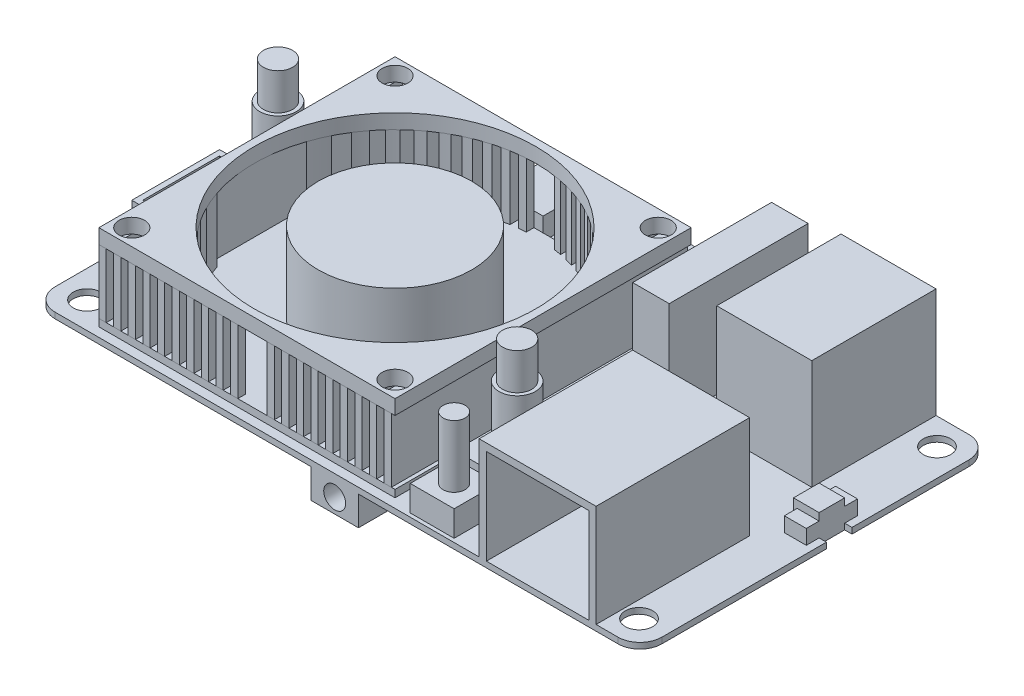
SolidWorks part; units mm, degrees
ref_plane "Front Plane" through (0, 0, 0) normal (0, 0, 1) x (1, 0, 0)
ref_plane "Top Plane" through (0, 0, 0) normal (0, 1, 0) x (1, 0, 0)
ref_plane "Right Plane" through (0, 0, 0) normal (1, 0, 0) x (0, 0, -1)
sketch "Sketch1" plane through (0, 0, 0) normal (0, 1, 0) x (1, 0, 0)
  line L0 (0, 0) -> (-83, 0)
  line L1 (-83, 0) -> (-83, 48)
  line L2 (-83, 48) -> (0, 48)
  line L3 (0, 48) -> (0, 0)
  line L4 (0, 24) -> (-83, 24) construction
  circle A0 centre (-79.25, 44.375) radius 1.875
  circle A1 centre (-79.25, 3.625) radius 1.875
  circle A2 centre (-3.75, 44.375) radius 1.875
  circle A3 centre (-3.75, 3.625) radius 1.875
  dimension "D1" = 20.375
  dimension "D2" = 20.375
  dimension "D3" = 3.75
  dimension "D4" = 3.75
  dimension "D5" = 83
  dimension "D6" = 48
extrude "Boss-Extrude1" add sketch "Sketch1" along normal blind 0.8
fillet "Fillet1" radius 3 4 edges at (-83, 0.4, -48) (0, 0.4, -48) (0, 0.4, 0) (-83, 0.4, 0)
sketch "Sketch2" plane through (0, 0.8, 0) normal (0, 1, 0) x (1, 0, 0)
  line L0 (-82.5, 13) -> (-77.4321, 13)
  line L1 (-77.4321, 13) -> (-77.4321, 25)
  line L2 (-77.4321, 25) -> (-82.5, 25)
  line L3 (-82.5, 25) -> (-82.5, 13)
  line L4 (-74, 40.5) -> (-74, 0)
  line L5 (-74, 0) -> (-33.5, 0)
  line L6 (-33.5, 0) -> (-33.5, 40.5)
  line L7 (-33.5, 40.5) -> (-74, 40.5)
  line L8 (-74, 20.25) -> (-53.75, 20.25) construction
  line L9 (-53.75, 20.25) -> (-53.75, 40.5) construction
  line L10 (-83, 45) -> (-83, 3) construction
  line L11 (-80, 0) -> (-3, 0) construction
  line L12 (-22, 0) -> (-22, 21)
  line L13 (-22, 21) -> (-6, 21)
  line L14 (-6, 21) -> (-6, 0)
  line L15 (-6, 0) -> (-22, 0)
  line L16 (-30, 48) -> (-30, 29)
  line L17 (-3, 48) -> (-80, 48) construction
  line L18 (-30, 29) -> (-25, 29)
  line L19 (-25, 29) -> (-25, 48)
  line L20 (-25, 48) -> (-30, 48)
  line L21 (-20.5, 48) -> (-20.5, 31)
  line L22 (-20.5, 31) -> (-7.5, 31)
  line L23 (-7.5, 31) -> (-7.5, 48)
  line L24 (-7.5, 48) -> (-20.5, 48)
  line L25 (0, 3) -> (0, 45) construction
  line L26 (-78.5, 32.5) -> (-74, 32.5)
  line L27 (-78.5, 25.5) -> (-74, 25.5)
  line L28 (-29, 15.7056) -> (-33.5, 15.7056)
  line L29 (-31.9171, 0.5) -> (-31.9171, 6.5)
  line L30 (-29, 8.7056) -> (-33.5, 8.7056)
  line L31 (-31.9171, 6.5) -> (-25.9171, 6.5)
  line L32 (-25.9171, 6.5) -> (-25.9171, 0.5)
  line L33 (-25.9171, 0.5) -> (-31.9171, 0.5)
  line L34 (-31.9171, 3.5) -> (-28.2034, 3.5) construction
  line L35 (-28.9171, 6.5) -> (-28.9171, 3.5) construction
  line L36 (-75.5, 43.75) -> (-68.5, 43.75)
  line L37 (-68.5, 43.75) -> (-68.5, 48.75)
  line L38 (-68.5, 48.75) -> (-75.5, 48.75)
  line L39 (-75.5, 48.75) -> (-75.5, 43.75)
  line L40 (-61.5, 41.75) -> (-61.5, 48.75)
  line L41 (-61.5, 48.75) -> (-55, 48.75)
  line L42 (-55, 48.75) -> (-55, 41.75)
  line L43 (-55, 41.75) -> (-61.5, 41.75)
  line L44 (-42, 48) -> (-42, 40.5)
  line L45 (-42, 40.5) -> (-37, 40.5)
  line L46 (-37, 40.5) -> (-37, 48)
  line L47 (-37, 48) -> (-42, 48)
  line L48 (0, 29) -> (-1, 29)
  line L49 (-1, 29) -> (-1, 25.5)
  line L50 (-1, 25.5) -> (0, 25.5)
  line L51 (-1, 29) -> (-1, 30.75)
  line L52 (-1, 30.75) -> (-4, 30.75)
  line L53 (-4, 30.75) -> (-4, 29)
  line L54 (-4, 29) -> (-4.5, 29)
  line L55 (-4.5, 29) -> (-4.5, 25.5)
  line L56 (-4.5, 25.5) -> (-4, 25.5)
  line L57 (-4, 25.5) -> (-4, 23.75)
  line L58 (-4, 23.75) -> (-1, 23.75)
  line L59 (-1, 23.75) -> (-1, 25.5)
  line L60 (-29, 27.25) -> (-29, 20.25)
  line L61 (-29, 20.25) -> (-27, 20.25)
  line L62 (-29, 27.25) -> (-27, 27.25)
  line L63 (-27, 27.25) -> (-27, 25.5)
  line L64 (-27, 25.5) -> (-26.5, 25.5)
  line L65 (-26.5, 25.5) -> (-26.5, 22)
  line L66 (-26.5, 22) -> (-27, 22)
  line L67 (-27, 22) -> (-27, 20.25)
  line L68 (-4, 29) -> (-1, 29)
  line L69 (-4, 25.5) -> (-1, 25.5)
  line L70 (-27, 25.5) -> (-29, 25.5)
  line L71 (-27, 22) -> (-29, 22)
  circle A0 centre (-53.75, 20.25) radius 19.25
  circle A1 centre (-71.75, 38.25) radius 1.75
  circle A2 centre (-35.75, 38.25) radius 1.75
  circle A3 centre (-35.75, 2.25) radius 1.75
  circle A4 centre (-71.75, 2.25) radius 1.75
  circle A5 centre (-53.75, 20.25) radius 10.5
  circle A6 centre (-78.5, 29) radius 2
  circle A7 centre (-28.9171, 3.5) radius 1.5
  circle A8 centre (-29, 12.2056) radius 2.5
  circle A9 centre (-78.5, 29) radius 2.5
  circle A10 centre (-78.5, 29) radius 3.5
  circle A11 centre (-29, 12.2056) radius 2
  circle A12 centre (-29, 12.2056) radius 3.5
  line M5 (-3, 48) -> (-80, 48)
  line M9 (-80, 0) -> (-3, 0)
  line M11 (0, 3) -> (0, 45)
  dimension "D1" = 9
  dimension "D3" = 2.25
  dimension "D5" = 6
  dimension "D17" = 4.5
  dimension "D18" = 0.5
  dimension "D19" = 6.5
  dimension "D35" = 1.75
  dimension "D2" = 0
  dimension "D4" = 2.25
  dimension "D6" = 16
  dimension "D7" = 21
  dimension "D8" = 13
  dimension "D9" = 5
  dimension "D10" = 4.5
  dimension "D11" = 7.5
  dimension "D12" = 0.5
  dimension "D13" = 13
  dimension "D14" = 12
  dimension "D15" = 4
  dimension "D16" = 4.5
  dimension "D20" = 7
  dimension "D21" = 0.75
  dimension "D22" = 0.75
  dimension "D23" = 1
  dimension "D24" = 3.5
  dimension "D25" = 19
  dimension "D26" = 17
  dimension "D27" = 19
  dimension "D28" = 7
  dimension "D29" = 5
  dimension "D30" = 13
  dimension "D31" = 7
  dimension "D32" = 7.5
  dimension "D33" = 7
  dimension "D34" = 5
  dimension "D36" = 2
  dimension "D37" = 3.5
  dimension "D38" = 1.75
  dimension "D39" = 0.5
extrude "Boss-Extrude2" add sketch "Sketch2" along normal blind 2 from offset 11 separate body contours L6 L7 L4 A0 M9 region at (-58, 0.8, -39.9272)
extrude "Boss-Extrude3" add sketch "Sketch2<3>" along normal blind 15 contours L22 L23 L21 M5 region at (-14, 0.8, -39.5)
sketch "Sketch2<3>" plane through (0, 0.8, 0) normal (0, 1, 0) x (1, 0, 0) same geometry as "Sketch2"
extrude "Boss-Extrude4" add sketch "Sketch2<4>" along normal blind 14 contours L14 L13 L12 M9 region at (-14, 0.8, -10.5)
sketch "Sketch2<4>" plane through (0, 0.8, 0) normal (0, 1, 0) x (1, 0, 0) same geometry as "Sketch2"
extrude "Boss-Extrude5" add sketch "Sketch2<5>" along normal blind 14 contours L18 L19 L16 M5 region at (-27.5, 0.8, -38.5)
sketch "Sketch2<5>" plane through (0, 0.8, 0) normal (0, 1, 0) x (1, 0, 0) same geometry as "Sketch2"
extrude "Boss-Extrude6" add sketch "Sketch2<6>" along normal blind 12 contours A7
sketch "Sketch2<6>" plane through (0, 0.8, 0) normal (0, 1, 0) x (1, 0, 0) same geometry as "Sketch2"
extrude "Boss-Extrude7" add sketch "Sketch2<7>" along normal blind 3.5 contours L33 L32 L31 L29 A7 region at (-31.8322, 0.8, -3.5)
sketch "Sketch2<7>" plane through (0, 0.8, 0) normal (0, 1, 0) x (1, 0, 0) same geometry as "Sketch2"
extrude "Boss-Extrude8" add sketch "Sketch2<8>" along normal blind 2.5 contours L39 L36 L37 M5 | L38 L39 L37 M5 region at (-72, 0.8, -45.875) region at (-72, 0.8, -48.375)
sketch "Sketch2<8>" plane through (0, 0.8, 0) normal (0, 1, 0) x (1, 0, 0) same geometry as "Sketch2"
extrude "Boss-Extrude9" add sketch "Sketch2<9>" along normal blind 3 contours L43 L42 L40 M5 | L42 L41 L40 M5 region at (-58.25, 0.8, -44.875) region at (-58.25, 0.8, -48.375)
sketch "Sketch2<9>" plane through (0, 0.8, 0) normal (0, 1, 0) x (1, 0, 0) same geometry as "Sketch2"
extrude "Boss-Extrude10" add sketch "Sketch2<10>" along normal blind 3.5 contours L7 L46 L44 M5 region at (-39.5, 0.8, -44.25)
sketch "Sketch2<10>" plane through (0, 0.8, 0) normal (0, 1, 0) x (1, 0, 0) same geometry as "Sketch2"
extrude "Boss-Extrude11" add sketch "Sketch2<11>" along normal blind 1 from offset 1.25 contours A10 L27 L4 L26 | A12 L28 L6 L30 | A10 | L7 L4 L5 L6 | A12 region at (-74.0832, 0.8, -29) region at (-31.25, 0.8, -15.6224)
sketch "Sketch2<11>" plane through (0, 0.8, 0) normal (0, 1, 0) x (1, 0, 0) same geometry as "Sketch2"
extrude "Boss-Extrude12" add sketch "Sketch2<12>" along normal blind 9 from surface contours A9 A6 | A8 A11 region at (-31.4293, 0.8, -12.2056) region at (-80.9293, 0.8, -29) starting at face at (-51.7143, 3.05, -23.3445)
sketch "Sketch2<12>" plane through (0, 0.8, 0) normal (0, 1, 0) x (1, 0, 0) same geometry as "Sketch2"
extrude "Boss-Extrude14" add sketch "Sketch2<13>" along normal blind 14 from offset 2.25 contours A6 | A11 region at (-78.5, 0.8, -29) region at (-29, 0.8, -12.2056)
sketch "Sketch2<13>" plane through (0, 0.8, 0) normal (0, 1, 0) x (1, 0, 0) same geometry as "Sketch2"
extrude "Boss-Extrude15" add sketch "Sketch2<14>" along normal blind 3 contours L58 L59 L49 L51 L52 L53 L54 L55 L56 L57 region at (-2.75, 0.8, -27.25)
sketch "Sketch2<14>" plane through (0, 0.8, 0) normal (0, 1, 0) x (1, 0, 0) same geometry as "Sketch2"
extrude "Cut-Extrude1" cut sketch "Sketch2<15>" against normal blind 3 contours L49 L50 L48 M11 region at (-0.5, 0.8, -27.25)
sketch "Sketch2<15>" plane through (0, 0.8, 0) normal (0, 1, 0) x (1, 0, 0) same geometry as "Sketch2"
extrude "Boss-Extrude16" add sketch "Sketch2<16>" along normal blind 2 contours L53 L68 L51 L52 | L69 L57 L58 L59 region at (-2.5, 0.8, -29.875) region at (-2.5, 0.8, -24.625)
sketch "Sketch2<16>" plane through (0, 0.8, 0) normal (0, 1, 0) x (1, 0, 0) same geometry as "Sketch2"
extrude "Boss-Extrude17" add sketch "Sketch2<17>" along normal blind 2 contours L67 L66 L65 L64 L63 L62 L60 L61 | L67 L71 L60 L61 | L70 L63 L62 L60 region at (-28, 0.8, -26.375) region at (-27.75, 0.8, -23.75) region at (-28, 0.8, -21.125)
sketch "Sketch2<17>" plane through (0, 0.8, 0) normal (0, 1, 0) x (1, 0, 0) same geometry as "Sketch2"
extrude "Boss-Extrude18" add sketch "Sketch2<18>" along normal blind 6 contours L71 L66 L65 L64 L70 L60 region at (-27.75, 0.8, -23.75)
sketch "Sketch2<18>" plane through (0, 0.8, 0) normal (0, 1, 0) x (1, 0, 0) same geometry as "Sketch2"
extrude "Boss-Extrude19" add sketch "Sketch2<19>" along normal blind 5.5 contours L2 L3 L0 L1 region at (-79.9661, 0.8, -19)
sketch "Sketch2<19>" plane through (0, 0.8, 0) normal (0, 1, 0) x (1, 0, 0) same geometry as "Sketch2"
chamfer "Chamfer1" distance 1 angle 45 1 edges at (-77.4321, 3.55, -25)
sketch "Sketch3" plane through (0, 3.05, 0) normal (0, 1, 0) x (1, 0, 0)
  line L0 (-74, 32.5) -> (-74, 25.5)
  line L1 (-73, 40.5) -> (-73, 32.5)
  line L2 (-73, 32.5) -> (-73, 25.5)
  line L3 (-73, 25.5) -> (-73, 0)
  line L4 (-72, 40.5) -> (-72, 32.5)
  line L5 (-72, 32.5) -> (-72, 25.5)
  line L6 (-72, 25.5) -> (-72, 0)
  line L7 (-71, 40.5) -> (-71, 32.5)
  line L8 (-71, 32.5) -> (-71, 25.5)
  line L9 (-71, 25.5) -> (-71, 0)
  line L10 (-70, 40.5) -> (-70, 32.5)
  line L11 (-70, 32.5) -> (-70, 25.5)
  line L12 (-74, 32.5) -> (-78.5, 32.5)
  line L13 (-78.5, 25.5) -> (-74, 25.5)
  line L14 (-74, 25.5) -> (-74, 0)
  line L15 (-74, 0) -> (-33.5, 0)
  line L16 (-33.5, 0) -> (-33.5, 8.7056)
  line L17 (-33.5, 8.7056) -> (-29, 8.7056)
  line L18 (-29, 15.7056) -> (-33.5, 15.7056)
  line L19 (-33.5, 15.7056) -> (-33.5, 40.5)
  line L20 (-33.5, 40.5) -> (-37, 40.5)
  line L21 (-37, 40.5) -> (-42, 40.5)
  line L22 (-42, 40.5) -> (-74, 40.5)
  line L23 (-74, 40.5) -> (-74, 32.5)
  line L24 (-74, 32.5) -> (-78.5, 32.5)
  line L25 (-78.5, 25.5) -> (-74, 25.5)
  line L26 (-74, 25.5) -> (-74, 0)
  line L27 (-74, 0) -> (-33.5, 0)
  line L28 (-33.5, 0) -> (-33.5, 8.7056)
  line L29 (-33.5, 8.7056) -> (-29, 8.7056)
  line L30 (-29, 15.7056) -> (-33.5, 15.7056)
  line L31 (-33.5, 15.7056) -> (-33.5, 40.5)
  line L32 (-33.5, 40.5) -> (-37, 40.5)
  line L33 (-37, 40.5) -> (-42, 40.5)
  line L34 (-42, 40.5) -> (-74, 40.5)
  line L35 (-74, 40.5) -> (-74, 32.5)
  line L36 (-70, 25.5) -> (-70, 0)
  line L37 (-69, 40.5) -> (-69, 32.5)
  line L38 (-69, 32.5) -> (-69, 25.5)
  line L39 (-69, 25.5) -> (-69, 0)
  line L40 (-68, 40.5) -> (-68, 32.5)
  line L41 (-68, 32.5) -> (-68, 25.5)
  line L42 (-68, 25.5) -> (-68, 0)
  line L43 (-67, 40.5) -> (-67, 32.5)
  line L44 (-67, 32.5) -> (-67, 25.5)
  line L45 (-67, 25.5) -> (-67, 0)
  line L46 (-66, 40.5) -> (-66, 32.5)
  line L47 (-66, 32.5) -> (-66, 25.5)
  line L48 (-66, 25.5) -> (-66, 0)
  line L49 (-65, 40.5) -> (-65, 32.5)
  line L50 (-65, 32.5) -> (-65, 25.5)
  line L51 (-65, 25.5) -> (-65, 0)
  line L52 (-64, 40.5) -> (-64, 32.5)
  line L53 (-64, 32.5) -> (-64, 25.5)
  line L54 (-64, 25.5) -> (-64, 0)
  line L55 (-63, 40.5) -> (-63, 32.5)
  line L56 (-63, 32.5) -> (-63, 25.5)
  line L57 (-63, 25.5) -> (-63, 0)
  line L58 (-62, 40.5) -> (-62, 32.5)
  line L59 (-62, 32.5) -> (-62, 25.5)
  line L60 (-62, 25.5) -> (-62, 0)
  line L61 (-61, 40.5) -> (-61, 32.5)
  line L62 (-61, 32.5) -> (-61, 25.5)
  line L63 (-61, 25.5) -> (-61, 0)
  line L64 (-60, 40.5) -> (-60, 32.5)
  line L65 (-60, 32.5) -> (-60, 25.5)
  line L66 (-60, 25.5) -> (-60, 0)
  line L67 (-59, 40.5) -> (-59, 32.5)
  line L68 (-59, 32.5) -> (-59, 25.5)
  line L69 (-59, 25.5) -> (-59, 0)
  line L70 (-58, 40.5) -> (-58, 32.5)
  line L71 (-58, 32.5) -> (-58, 25.5)
  line L72 (-58, 25.5) -> (-58, 0)
  line L73 (-57, 40.5) -> (-57, 32.5)
  line L74 (-57, 32.5) -> (-57, 25.5)
  line L75 (-57, 25.5) -> (-57, 0)
  line L76 (-56, 40.5) -> (-56, 32.5)
  line L77 (-56, 32.5) -> (-56, 25.5)
  line L78 (-56, 25.5) -> (-56, 0)
  line L79 (-55, 40.5) -> (-55, 32.5)
  line L80 (-55, 32.5) -> (-55, 25.5)
  line L81 (-55, 25.5) -> (-55, 0)
  line L82 (-54, 40.5) -> (-54, 32.5)
  line L83 (-54, 32.5) -> (-54, 25.5)
  line L84 (-54, 25.5) -> (-54, 0)
  line L85 (-53, 40.5) -> (-53, 32.5)
  line L86 (-53, 32.5) -> (-53, 25.5)
  line L87 (-53, 25.5) -> (-53, 0)
  line L88 (-52, 40.5) -> (-52, 32.5)
  line L89 (-52, 32.5) -> (-52, 25.5)
  line L90 (-52, 25.5) -> (-52, 0)
  line L91 (-51, 40.5) -> (-51, 32.5)
  line L92 (-51, 32.5) -> (-51, 25.5)
  line L93 (-51, 25.5) -> (-51, 0)
  line L94 (-50, 40.5) -> (-50, 32.5)
  line L95 (-50, 32.5) -> (-50, 25.5)
  line L96 (-50, 25.5) -> (-50, 0)
  line L97 (-49, 40.5) -> (-49, 32.5)
  line L98 (-49, 32.5) -> (-49, 25.5)
  line L99 (-49, 25.5) -> (-49, 0)
  line L100 (-48, 40.5) -> (-48, 32.5)
  line L101 (-48, 32.5) -> (-48, 25.5)
  line L102 (-48, 25.5) -> (-48, 0)
  line L103 (-47, 40.5) -> (-47, 32.5)
  line L104 (-47, 32.5) -> (-47, 25.5)
  line L105 (-47, 25.5) -> (-47, 0)
  line L106 (-46, 40.5) -> (-46, 32.5)
  line L107 (-46, 32.5) -> (-46, 25.5)
  line L108 (-46, 25.5) -> (-46, 0)
  line L109 (-45, 40.5) -> (-45, 32.5)
  line L110 (-45, 32.5) -> (-45, 25.5)
  line L111 (-45, 25.5) -> (-45, 0)
  line L112 (-44, 40.5) -> (-44, 32.5)
  line L113 (-44, 32.5) -> (-44, 25.5)
  line L114 (-44, 25.5) -> (-44, 0)
  line L115 (-43, 40.5) -> (-43, 32.5)
  line L116 (-43, 32.5) -> (-43, 25.5)
  line L117 (-43, 25.5) -> (-43, 0)
  line L118 (-42, 40.5) -> (-42, 32.5)
  line L119 (-42, 32.5) -> (-42, 25.5)
  line L120 (-42, 25.5) -> (-42, 0)
  line L121 (-41, 40.5) -> (-41, 32.5)
  line L122 (-41, 32.5) -> (-41, 25.5)
  line L123 (-41, 25.5) -> (-41, 0)
  line L124 (-40, 40.5) -> (-40, 32.5)
  line L125 (-40, 32.5) -> (-40, 25.5)
  line L126 (-40, 25.5) -> (-40, 0)
  line L127 (-39, 40.5) -> (-39, 32.5)
  line L128 (-39, 32.5) -> (-39, 25.5)
  line L129 (-39, 25.5) -> (-39, 0)
  line L130 (-38, 40.5) -> (-38, 32.5)
  line L131 (-38, 32.5) -> (-38, 25.5)
  line L132 (-38, 25.5) -> (-38, 0)
  line L133 (-37, 40.5) -> (-37, 32.5)
  line L134 (-37, 32.5) -> (-37, 25.5)
  line L135 (-37, 25.5) -> (-37, 0)
  line L136 (-36, 40.5) -> (-36, 32.5)
  line L137 (-36, 32.5) -> (-36, 25.5)
  line L138 (-36, 25.5) -> (-36, 0)
  line L139 (-35, 40.5) -> (-35, 32.5)
  line L140 (-35, 32.5) -> (-35, 25.5)
  line L141 (-35, 25.5) -> (-35, 0)
  line L142 (-34, 40.5) -> (-34, 32.5)
  line L143 (-34, 32.5) -> (-34, 25.5)
  line L144 (-34, 25.5) -> (-34, 0)
  circle A0 centre (-53.75, 20.25) radius 19.25 construction
  circle A1 centre (-53.75, 20.25) radius 19.25
  arc A2 (-78.5, 32.5) -> (-78.5, 25.5) centre (-78.5, 29) ccw
  arc A3 (-29, 8.7056) -> (-29, 15.7056) centre (-29, 12.2056) ccw
  arc A4 (-78.5, 32.5) -> (-78.5, 25.5) centre (-78.5, 29) ccw
  arc A5 (-29, 8.7056) -> (-29, 15.7056) centre (-29, 12.2056) ccw
  line M139 (-74, 25.5) -> (-74, 0)
  line M140 (-74, 0) -> (-33.5, 0)
  line M148 (-42, 40.5) -> (-74, 40.5)
  line M149 (-74, 40.5) -> (-74, 32.5)
  dimension "D2" = 41
  dimension "D1" = 0
extrude "Boss-Extrude23" add sketch "Sketch3" along normal blind 8.75 separate body contours L3 L2 L1 L0 M148 M149 M139 M140 | A1 L6 L9 M140 | A1 L36 L27 L39 | A1 L42 L27 L45 | A1 L48 L27 L51 | A1 L54 L27 L57 | A1 L60 L27 L63 | A1 L66 L27 L69 | A1 L72 L27 L75 | A1 L78 L27 L81 | A1 L8 L7 L4 L5 M148 | A1 L38 L37 L34 L10 L11 | A1 L43 L34 L40 | A1 L49 L34 L46 | A1 L55 L34 L52 | A1 L61 L34 L58 | A1 L67 L34 L64 | A1 L73 L34 L70 | A1 L79 L34 L76 | A1 L93 L96 M140 | A1 L99 L102 M140 | A1 L105 L108 M140 | A1 L111 L114 M140 | A1 L117 L120 M140 | A1 L123 L126 M140 | A1 L129 L132 M140 | A1 L135 L138 M140 | A1 L141 L144 L143 L142 L32 L139 L140 M140 | A1 L137 L136 L32 L133 L134 | A1 L131 L130 L33 L127 | A1 L124 L33 L121 | A1 L118 L115 M148 | A1 L112 L34 L109 | A1 L106 L34 L103 | A1 L100 L34 L97 | A1 L94 L34 L91 region at (-73.5, 3.05, -20.25) region at (-71.5156, 3.05, -34.062) region at (-71.5156, 3.05, -6.438) region at (-69.5129, 3.05, -35.8941) region at (-69.5129, 3.05, -4.6059) region at (-67.5125, 3.05, -37.1015) region at (-67.5125, 3.05, -3.3985) region at (-65.5128, 3.05, -37.9918) region at (-65.5128, 3.05, -2.5082) region at (-63.5134, 3.05, -38.6685) region at (-63.5134, 3.05, -1.8315) region at (-61.5139, 3.05, -39.181) region at (-61.5139, 3.05, -1.319) region at (-59.5139, 3.05, -39.5572) region at (-59.5139, 3.05, -0.9428) region at (-57.5121, 3.05, -39.8133) region at (-57.5121, 3.05, -0.6867) region at (-55.507, 3.05, -39.9587) region at (-55.507, 3.05, -0.5413) region at (-50.4888, 3.05, -39.8597) region at (-50.4888, 3.05, -0.6403) region at (-48.4864, 3.05, -39.632) region at (-48.4864, 3.05, -0.868) region at (-46.486, 3.05, -39.2871) region at (-46.486, 3.05, -1.2129) region at (-44.4865, 3.05, -38.8107) region at (-44.4865, 3.05, -1.6893) region at (-42.487, 3.05, -38.1786) region at (-42.487, 3.05, -2.3214) region at (-40.4874, 3.05, -37.3483) region at (-40.4874, 3.05, -3.1517) region at (-38.4873, 3.05, -36.2356) region at (-38.4873, 3.05, -4.2644) region at (-36.4856, 3.05, -34.6198) region at (-36.4856, 3.05, -5.8802) region at (-34.4768, 3.05, -20.25)
extrude "Boss-Extrude24" add sketch "Sketch2<20>" along normal blind 11 from surface contours A5 region at (-53.75, 0.8, -20.25) starting at face at (-51.7143, 3.05, -23.3445)
sketch "Sketch2<20>" plane through (0, 0.8, 0) normal (0, 1, 0) x (1, 0, 0) same geometry as "Sketch2"
sketch "Sketch4" plane through (0, 0, 0) normal (0, -1, 0) x (1, 0, 0)
  line L0 (-82.5, -41) -> (-78, -41)
  line L1 (-78, -41) -> (-78, -32.5)
  line L2 (-78, -32.5) -> (-82.5, -32.5)
  line L3 (-82.5, -32.5) -> (-82.5, -41)
  line L4 (-74.5, -10) -> (-74.5, -15)
  line L5 (-74.5, -15) -> (-63.5, -15)
  line L6 (-63.5, -15) -> (-63.5, -10)
  line L7 (-63.5, -10) -> (-74.5, -10)
  line L8 (-63, -2) -> (-63, -20)
  line L9 (-63, -20) -> (-50, -20)
  line L10 (-50, -20) -> (-50, -2)
  line L11 (-50, -2) -> (-63, -2)
  line L12 (-62, -3.5) -> (-62, -16.5)
  line L13 (-62, -16.5) -> (-51, -16.5)
  line L14 (-51, -16.5) -> (-51, -3.5)
  line L15 (-51, -3.5) -> (-62, -3.5)
  line L16 (-45, -13) -> (-45, 0)
  line L17 (-45, 0) -> (-38.5, 0)
  line L18 (-80, 0) -> (-3, 0) construction
  line L19 (-38.5, 0) -> (-38.5, -13)
  line L20 (-45, -13) -> (-38.5, -13)
  line L21 (-83, -45) -> (-83, -3) construction
  line L22 (-3, -48) -> (-80, -48) construction
  line L23 (-6, -21) -> (-6, 0) construction
  line L24 (-6, -21) -> (-6, 0)
  line L25 (-22, 0) -> (-22, -21) construction
  line L26 (-22, 0) -> (-22, -21)
  circle A0 centre (-20.25, -10) radius 1.5
  circle A1 centre (-7.75, -10) radius 1.5
  circle A2 centre (-29, -12.2056) radius 2 construction
  circle A3 centre (-78.5, -29) radius 2 construction
  circle A4 centre (-29, -12.2056) radius 2
  circle A5 centre (-78.5, -29) radius 2
  circle A6 centre (-78.5, -29) radius 1.5
  circle A7 centre (-29, -12.2056) radius 1.5
  line M6 (-3, 0) -> (-80, 0)
  dimension "D1" = 8.5
  dimension "D5" = 20
  dimension "D2" = 0.5
  dimension "D3" = 4.5
  dimension "D4" = 7
  dimension "D6" = 1
  dimension "D7" = 1
  dimension "D8" = 13
  dimension "D9" = 2
  dimension "D10" = 1.5
  dimension "D11" = 3.5
  dimension "D12" = 13
  dimension "D13" = 0.5
  dimension "D14" = 11
  dimension "D15" = 5
  dimension "D16" = 10
  dimension "D17" = 5
  dimension "D18" = 6.5
  dimension "D19" = 13
  dimension "D20" = 1.75
  dimension "D21" = 1.75
  dimension "D22" = 10
  dimension "D23" = 10
extrude "Boss-Extrude25" add sketch "Sketch4" along normal blind 4.5 contours L2 L3 L0 L1 region at (-80.25, 0, -36.75)
extrude "Boss-Extrude26" add sketch "Sketch4<3>" along normal blind 3 contours L6 L7 L4 L5 region at (-69, 0, -12.5)
sketch "Sketch4<3>" plane through (0, 0, 0) normal (0, -1, 0) x (1, 0, 0) same geometry as "Sketch4"
extrude "Boss-Extrude27" add sketch "Sketch4<4>" along normal blind 2.5 contours L14 L15 L12 L13 region at (-56.5, 0, -10)
sketch "Sketch4<4>" plane through (0, 0, 0) normal (0, -1, 0) x (1, 0, 0) same geometry as "Sketch4"
extrude "Boss-Extrude28" add sketch "Sketch4<5>" along normal blind 2 contours L10 L11 L8 L9 L15 L14 L13 L12 region at (-56.5, 0, -2.222)
sketch "Sketch4<5>" plane through (0, 0, 0) normal (0, -1, 0) x (1, 0, 0) same geometry as "Sketch4"
extrude "Boss-Extrude29" add sketch "Sketch4<6>" along normal blind 4 contours L16 L20 L19 M6 region at (-41.75, 0, -6.5)
sketch "Sketch4<6>" plane through (0, 0, 0) normal (0, -1, 0) x (1, 0, 0) same geometry as "Sketch4"
extrude "Boss-Extrude30" add sketch "Sketch4<7>" along normal blind 4 draft 5 contours A6 | A7 region at (-78.5, 0, -29) region at (-29, 0, -12.2056)
sketch "Sketch4<7>" plane through (0, 0, 0) normal (0, -1, 0) x (1, 0, 0) same geometry as "Sketch4"
extrude "Boss-Extrude31" add sketch "Sketch4<8>" along normal blind 2 draft 5 contours A0 | A1 region at (-20.25, 0, -10) region at (-7.75, 0, -10)
sketch "Sketch4<8>" plane through (0, 0, 0) normal (0, -1, 0) x (1, 0, 0) same geometry as "Sketch4"
sketch "Sketch5" plane through (0, 0, 0) normal (0, 0, 1) x (1, 0, 0)
  line L6 (-21, 0.8) -> (-7, 0.8)
  line L9 (-7, 13.8) -> (-7, 0.8)
  line L10 (-21, 13.8) -> (-7, 13.8)
  line L11 (-21, 0.8) -> (-21, 13.8)
  line L12 (-7, 13.8) -> (-7, 0.8)
  line L13 (-21, 13.8) -> (-7, 13.8)
  line L14 (-21, 0.8) -> (-21, 13.8)
  dimension "D1" = 1
extrude "Cut-Extrude2" cut sketch "Sketch5" against normal offset from surface (19 mm away) 2 up to face at (-14, 7.8, -21)
sketch "Sketch6" plane through (0, 0, -48) normal (0, 0, -1) x (-1, 0, 0)
  line L6 (8.5, 8.8) -> (19.5, 8.8)
  line L7 (8.5, 6.8) -> (19.5, 6.8)
  line L8 (8.5, 0.8) -> (19.5, 0.8)
  line L9 (19.5, 14.8) -> (19.5, 0.8)
  line L10 (8.5, 14.8) -> (19.5, 14.8)
  line L11 (8.5, 0.8) -> (8.5, 14.8)
  line L12 (19.5, 14.8) -> (19.5, 8.8)
  line L13 (8.5, 14.8) -> (19.5, 14.8)
  line L14 (8.5, 0.8) -> (8.5, 6.8)
  line L16 (25.5, 0.8) -> (29.5, 0.8)
  line L17 (8.5, 8.8) -> (8.5, 14.8)
  line L18 (19.5, 6.8) -> (19.5, 0.8)
  line L21 (29.5, 14.3) -> (29.5, 0.8)
  line L22 (25.5, 14.3) -> (29.5, 14.3)
  line L23 (25.5, 0.8) -> (25.5, 14.3)
  line L24 (29.5, 14.3) -> (29.5, 0.8)
  line L25 (25.5, 14.3) -> (29.5, 14.3)
  line L26 (25.5, 0.8) -> (25.5, 14.3)
  dimension "D2" = 2
  dimension "D1" = 1
  dimension "D3" = 0.5
extrude "Cut-Extrude3" cut sketch "Sketch6" against normal offset from surface (15 mm away) 2 up to face at (-14, 8.3, -31)
sketch "Sketch7" plane through (0, 0, 0) normal (0, 0, 1) x (1, 0, 0)
  line L0 (-45, 0) -> (-38.5, -4) construction
  circle A0 centre (-41.75, -2) radius 1.5
  dimension "D1" = 3
extrude "Cut-Extrude4" cut sketch "Sketch7" against normal offset from surface (11 mm away) 2 up to face at (-41.75, -2, -13)
sketch "Sketch8" plane through (0, 6.3, 0) normal (0, 1, 0) x (1, 0, 0)
  line L10 (-78.1821, 13.75) -> (-78.1821, 23.6893)
  line L11 (-78.1821, 23.6893) -> (-78.7428, 24.25)
  line L12 (-78.7428, 24.25) -> (-81.75, 24.25)
  line L13 (-81.75, 24.25) -> (-81.75, 13.75)
  line L14 (-81.75, 13.75) -> (-78.1821, 13.75)
  line L15 (-78.1821, 13.75) -> (-78.1821, 23.6893)
  line L16 (-78.1821, 23.6893) -> (-78.7428, 24.25)
  line L17 (-78.7428, 24.25) -> (-81.75, 24.25)
  line L18 (-81.75, 24.25) -> (-81.75, 13.75)
  line L19 (-81.75, 13.75) -> (-78.1821, 13.75)
  dimension "D1" = 0.75
extrude "Cut-Extrude5" cut sketch "Sketch8" against normal up to surface (5.5 mm away) up to face at (-28.2216, 0.8, -32.1136)
ref_plane "central_plane" through (-41.5, 0, 0) normal (-1, 0, 0) x (0, 0, 1)
